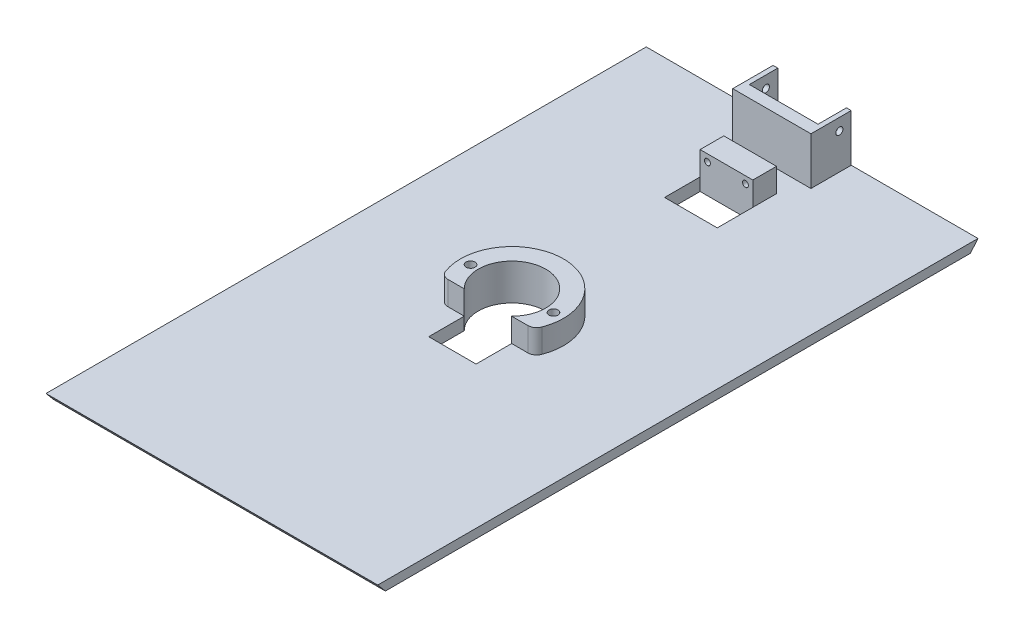
SolidWorks part; units mm, degrees
material "PLA"
ref_plane "Plan de face" through (0, 0, 0) normal (0, 0, 1) x (1, 0, 0)
ref_plane "Plan de dessus" through (0, 0, 0) normal (0, 1, 0) x (1, 0, 0)
ref_plane "Plan de droite" through (0, 0, 0) normal (1, 0, 0) x (0, 0, -1)
sketch "Esquisse1" plane through (0, 0, 0) normal (1, 0, 0) x (0, -1, 0)
  line L2 (0, -123.4336) -> (0, 123.4336)
  line L4 (-3.8302, -126.6475) -> (-3.8302, 126.6475)
  line L5 (-4, 127.051) -> (0, 123.6946) construction
  line L6 (-4, -127.051) -> (0, -123.6946) construction
  line L7 (0, -123.6946) -> (0, 123.6946) construction
  line L10 (0, 123.4336) -> (-3.8302, 126.6475)
  line L19 (0, -123.4336) -> (-3.8302, -126.6475)
  point P0 (0, 0)
  dimension "D1" = 0.2
  dimension "D2" = 5
  dimension "D3" = 0.2
extrude "Boss.-Extru.1" add sketch "Esquisse1" along normal up to surface (70 mm away) and the other way up to surface (70 mm away)
sketch "Esquisse12" plane through (0, 0, 0) normal (0, -1, 0) x (-1, 0, 0)
  line L0 (-70, 123.4336) -> (70, 123.4336) construction
  line L1 (-64.8, -123.4336) -> (64.8, -123.4336)
  line L2 (-64.8, -123.4336) -> (-64.8, 123.4336)
  line L3 (-64.8, 123.4336) -> (64.8, 123.4336)
  line L4 (64.8, -123.4336) -> (64.8, 123.4336)
  line L5 (-64.8, -123.4336) -> (64.8, 123.4336) construction
  line L6 (-64.8, 123.4336) -> (64.8, -123.4336) construction
  line L7 (70, -123.4336) -> (70, 123.4336) construction
  point P0 (0, 0)
  dimension "D1" = 5.2
extrude "Boss.-Extru.7" add sketch "Esquisse12" along normal blind 1.5
chamfer "Chanfrein1" distance 1.5 angle 50 2 edges at (0, -1.5, 123.4336) (0, -1.5, -123.4336)
sketch "Esquisse4" plane through (95, 0, 0) normal (0, -1, 0) x (-1, 0, 0)
  line L1 (105, -25.152) -> (85, -25.152)
  line L2 (105, -25.152) -> (105, -10.152)
  line L4 (85, -25.152) -> (85, -10.152)
  line L5 (105, -25.152) -> (85, -10.152) construction
  line L6 (105, -10.152) -> (85, -25.152) construction
  arc A0 (105, -10.152) -> (85, -10.152) centre (95, 0) ccw
  point P3 (95, -17.652)
  dimension "D1" = 28.5
  dimension "D2" = 20
  dimension "D3" = 15
extrude "Enlèv. mat.-Extru.1" cut sketch "Esquisse4" against normal through all both and the other way through all
sketch "Esquisse5" plane through (95, 3.8302, 0) normal (0, -1, 0) x (-1, 0, 0)
  line L8 (105, -10.152) -> (115.8757, -16.9035) construction
  line L9 (115.8757, -16.9035) -> (71.5835, -18.4808) construction
  line L10 (85, -10.152) -> (71.5835, -18.4808) construction
  line L11 (74.6722, -7.7357) -> (43.6733, -26.9794) construction
  line L12 (140.7576, -23.5222) -> (43.6733, -26.9794) construction
  line L14 (115.3278, -7.7357) -> (140.7576, -23.5222) construction
  line L15 (105, -10.152) -> (111.823, -10.152)
  line L16 (85, -10.152) -> (78.177, -10.152)
  arc A0 (105, -10.152) -> (85, -10.152) centre (95, 0) ccw
  arc A1 (115.3278, -7.7357) -> (74.6722, -7.7357) centre (95, 0) ccw
  circle A2 centre (77.5, 0) radius 1.9
  circle A3 centre (112.5, 0) radius 1.9
  arc A4 (111.823, -10.152) -> (115.3278, -7.7357) centre (111.823, -6.402) ccw
  arc A5 (74.6722, -7.7357) -> (78.177, -10.152) centre (78.177, -6.402) ccw
  dimension "D2" = 3.8
  dimension "D3" = 35
  dimension "D4" = 17.5
  dimension "D1" = 7.5
extrude "Boss.-Extru.4" add sketch "Esquisse5" against normal blind 10
sketch "Esquisse6" plane through (0, 0, 0) normal (0, -1, 0) x (-1, 0, 0)
  line L1 (-11.12, 90.5) -> (11.12, 90.5)
  line L2 (-11.12, 90.5) -> (-11.12, 75.5)
  line L3 (-11.12, 75.5) -> (11.12, 75.5)
  line L4 (11.12, 90.5) -> (11.12, 75.5)
  line L5 (-11.12, 90.5) -> (11.12, 75.5) construction
  line L6 (-11.12, 75.5) -> (11.12, 90.5) construction
  point P0 (0, 83)
  dimension "D1" = 22.24
  dimension "D2" = 15
  dimension "D3" = 83
extrude "Enlèv. mat.-Extru.2" cut sketch "Esquisse6" against normal through all both and the other way through all
sketch "Esquisse7" plane through (0, 3.8302, 0) normal (0, 1, 0) x (1, 0, 0)
  line L0 (-11.12, 90.5) -> (11.12, 90.5) construction
  line L1 (11.12, 100.5) -> (-11.12, 100.5)
  line L2 (11.12, 100.5) -> (11.12, 90.5)
  line L3 (11.12, 90.5) -> (-11.12, 90.5)
  line L4 (-11.12, 100.5) -> (-11.12, 90.5)
  line L5 (11.12, 90.5) -> (11.12, 75.5) construction
  line L6 (-11.12, 75.5) -> (-11.12, 90.5) construction
  dimension "D1" = 10
extrude "Boss.-Extru.5" add sketch "Esquisse7" along normal up to surface (10 mm away)
sketch "Esquisse8" plane through (0, 0, -90.5) normal (0, 0, 1) x (1, 0, 0)
  line L0 (11.12, 13.8302) -> (-11.12, 13.8302) construction
  line L1 (-11.12, 13.8302) -> (-11.12, 3.8302) construction
  line L2 (11.12, 13.8302) -> (11.12, 3.8302) construction
  circle A0 centre (-8.02, 10.8302) radius 1.25
  circle A1 centre (8.02, 10.8302) radius 1.25
  dimension "D1" = 2.5
  dimension "D2" = 3
  dimension "D3" = 3.1
  dimension "D4" = 3.1
extrude "Enlèv. mat.-Extru.3" cut sketch "Esquisse8" against normal through all
sketch "Esquisse9" plane through (0, 3.8302, 0) normal (0, 1, 0) x (1, 0, 0)
  line L0 (70, 126.6475) -> (-70, 126.6475) construction
  line L1 (-14.5, 114.6475) -> (14.5, 114.6475)
  line L2 (-14.5, 114.6475) -> (-14.5, 126.6475)
  line L4 (14.5, 114.6475) -> (14.5, 126.6475)
  line L5 (-14.5, 114.6475) -> (14.5, 126.6475) construction
  line L6 (-14.5, 126.6475) -> (14.5, 114.6475) construction
  line L7 (14.5, 126.6475) -> (16.5, 126.6475)
  line L8 (-16.5, 109.6475) -> (16.5, 109.6475)
  line L9 (-16.5, 109.6475) -> (-16.5, 126.6475)
  line L10 (-16.5, 126.6475) -> (-14.5, 126.6475)
  line L11 (16.5, 109.6475) -> (16.5, 126.6475)
  line L12 (-16.5, 109.6475) -> (16.5, 126.6475) construction
  line L13 (-16.5, 126.6475) -> (16.5, 109.6475) construction
  point P0 (0, 120.6475)
  point P7 (0, 118.1475)
  dimension "D1" = 29
  dimension "D2" = 12
  dimension "D3" = 2
  dimension "D4" = 5
extrude "Boss.-Extru.6" add sketch "Esquisse9" along normal blind 20
sketch "Esquisse11" plane through (0, 0, 0) normal (1, 0, 0) x (0, 0, -1)
  line L0 (126.6475, 23.8302) -> (126.6475, 3.8302) construction
  line L1 (109.6475, 3.8302) -> (126.6475, 3.8302) construction
  circle A0 centre (121.6475, 18.8302) radius 1.5
  dimension "D1" = 3
  dimension "D2" = 5
  dimension "D3" = 15
extrude "Enlèv. mat.-Extru.4" cut sketch "Esquisse11" against normal through all both and the other way through all
